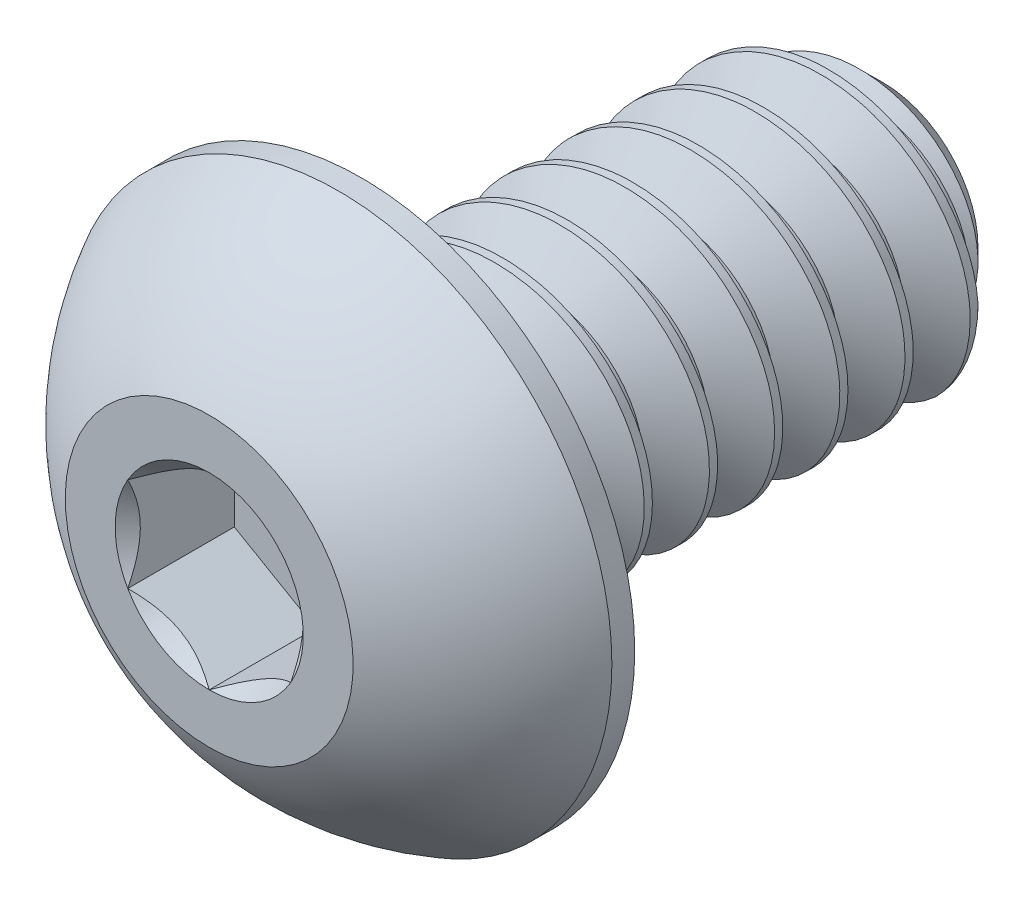
SolidWorks part; units mm, degrees
ref_plane "Front" through (0, 0, 0) normal (0, 0, 1) x (1, 0, 0)
ref_plane "Top" through (0, 0, 0) normal (0, 1, 0) x (1, 0, 0)
ref_plane "Right" through (0, 0, 0) normal (1, 0, 0) x (0, 0, -1)
sketch "Sketch1" plane through (0, 0, 0) normal (1, 0, 0) x (0, 0, -1)
  line L2 (1.8542, 1.7526) -> (8.2042, 1.7526)
  line L3 (8.2042, 1.7526) -> (8.2042, 0)
  line L4 (8.2042, 0) -> (1.8542, 0)
  line L6 (1.5761, 3.3274) -> (1.8542, 3.3274) construction
  line L7 (8.2042, 1.7526) -> (8.2042, -1.7526) construction
  line L8 (0, 0) -> (1.8542, 0) construction
  line L9 (1.8542, 3.3274) -> (1.8542, -3.3274) construction
  line L11 (1.8542, 1.7526) -> (1.8542, 0)
  line L13 (0, 0.9922) -> (0, -0.9922) construction
  line L14 (0, 0.9922) -> (0, 1.7526) construction
  arc A3 (0, 1.7526) -> (1.5761, 3.3274) centre (3.326, 0) cw construction
  dimension "D1" = 0.2781
  dimension "Head Ht" = 1.8542
  dimension "Head Dia" = 6.6548
  dimension "Dia" = 3.5052
  dimension "Lg" = 6.35
  dimension "Hex" = 1.9844
revolve "Revolve1" add sketch "Sketch1" angle 360 mid plane about L4
sketch "Sketch3" plane through (0, 0, -8.2042) normal (0, 0, -1) x (-1, 0, 0)
  circle A0 centre (0, 0) radius 1.7526
curve "Helix/Spiral1" pitch 0.7937 height 7.1437 turns 9
sketch "Sketch2" plane through (0, 0, 0) normal (1, 0, 0) x (0, 0, -1)
  line L0 (8.2042, 1.7526) -> (8.8987, 1.7526)
  line L1 (8.8987, 1.7526) -> (8.6011, 1.237)
  line L2 (8.6011, 1.237) -> (8.5019, 1.237)
  line L3 (8.5019, 1.237) -> (8.2042, 1.7526)
  line L4 (8.353, 1.4948) -> (8.7499, 1.4948) construction
  dimension "D1" = 60
  dimension "D2" = 0.0992
  dimension "D3" = 0.3969
chamfer "Chamfer1" distance 0.5953 angle 45 1 edges at (0, 1.7526, -8.2042)
sweep "Cut-Sweep1" cut profiles "Sketch2" path "Helix/Spiral1" align with end faces yes
sketch "Sketch7" plane through (0, 0, 0) normal (1, 0, 0) x (0, 0, -1)
  line L6 (1.5761, 3.3274) -> (1.8542, 3.3274) construction
  line L8 (0, 0) -> (1.8542, 0) construction
  line L11 (1.8542, 3.3274) -> (1.8542, -3.3274) construction
  line L12 (1.5761, 3.3274) -> (1.8542, 3.3274)
  line L13 (0, 0) -> (1.8542, 0)
  line L14 (0, 0.9922) -> (0, -0.9922) construction
  line L15 (1.8542, 3.3274) -> (1.8542, 0)
  line L16 (0, 1.7526) -> (0, 0)
  arc A2 (1.5761, 3.3274) -> (0, 1.7526) centre (3.326, 0) ccw construction
  arc A3 (1.5761, 3.3274) -> (0, 1.7526) centre (3.326, 0) ccw
revolve "Revolve2" add sketch "Sketch7" angle 360 mid plane about L13
sketch "Sketch5" plane through (0, 0, 0) normal (0, 0, 1) x (1, 0, 0)
  line L1 (0.9922, -0.5728) -> (0.9922, 0.5728)
  line L2 (0.9922, 0.5728) -> (0, 1.1457)
  line L3 (0, 1.1457) -> (-0.9922, 0.5728)
  line L4 (-0.9922, 0.5728) -> (-0.9922, -0.5728)
  line L5 (-0.9922, -0.5728) -> (0, -1.1457)
  line L6 (0, -1.1457) -> (0.9922, -0.5728)
  circle A0 centre (0, 0) radius 0.9922 construction
extrude "Cut-Extrude2" cut sketch "Sketch5" against normal blind 1.2979
sketch "Sketch6" plane through (0, 0, 0) normal (0, 0, 1) x (1, 0, 0)
  circle A0 centre (0, 0) radius 1.1457
extrude "Cut-Extrude3" cut sketch "Sketch6" against normal blind 1.2979 draft 45
sketch "Sketch9" [suppressed] plane through (0, 0, -1.4986) normal (0, 0, 1) x (1, 0, 0)
  circle A2 centre (0, 0) radius 1.4224
extrude "Boss-Extrude2" [suppressed] add sketch "Sketch9" against normal offset from surface (12.7 mm away) 31.75
sketch "Sketch10" plane through (0, 0, 0) normal (1, 0, 0) x (0, 0, -1)
  line L0 (8.2042, 1.7526) -> (8.2042, -1.7526) construction
  point P0 (7.0136, -1.7526)
  dimension "D1" = 1.1906
equation "\"D3@Helix/Spiral1\" = \"Lg@Sketch1\" + \"D4@Helix/Spiral1\""
equation "\"D2@Sketch2\" = \"D4@Helix/Spiral1\" * .125"
equation "\"D3@Sketch2\" = \"D4@Helix/Spiral1\" * .5"
equation "\"D1@Chamfer1\" = \"D4@Helix/Spiral1\" * .75"
equation "\"D1@Cut-Extrude2\" = \"Head Ht@Sketch1\" * .7"
equation "\"D1@Sketch1\" = \"Head Ht@Sketch1\" * .15"
equation "\"D1@Sketch10\" = \"D4@Helix/Spiral1\" * 1.5"
equation "\"D1@Cut-Extrude3\" = \"D1@Cut-Extrude2\""
